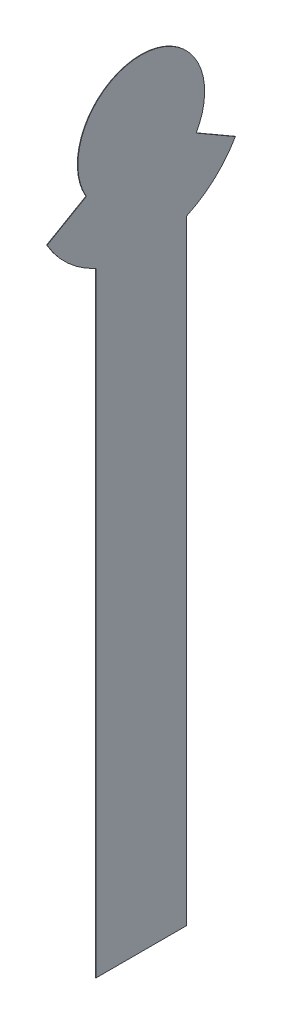
SolidWorks part; units mm, degrees
ref_plane "Front Plane" through (0, 0, 0) normal (0, 0, 1) x (1, 0, 0)
ref_plane "Top Plane" through (0, 0, 0) normal (0, 1, 0) x (1, 0, 0)
ref_plane "Right Plane" through (0, 0, 0) normal (1, 0, 0) x (0, 0, -1)
sketch "Sketch1" plane through (0, 0, 0) normal (1, 0, 0) x (0, 0, -1)
  line L0 (0, -35) -> (0, -393.6) construction
  line L1 (-25, -393.6) -> (25, -393.6) construction
  line L2 (-25, -393.6) -> (-25, -54.5436)
  line L3 (25, -393.6) -> (25, -54.5436)
  line L4 (-30.3109, -17.5) -> (-51.9615, -30)
  line L5 (30.3109, -17.5) -> (51.9615, -30)
  line L6 (-14.9027, 0) -> (13.6443, 0) construction
  line L7 (-25, -393.6) -> (25, -393.6)
  arc A0 (-51.9615, -30) -> (51.9615, -30) centre (0, 0) ccw
  circle A1 centre (0, 0) radius 35
  point P8 (0, -393.6)
  dimension "D1" = 120
  dimension "D2" = 70
  dimension "D3" = 393.6
  dimension "D4" = 50
  dimension "D5" = 30
  dimension "D6" = 30
extrude "Boss-Extrude1" add sketch "Sketch1" against normal blind 0.25 contours A0 L2 L7 L3 | A1 L4 A0 L5 | A1 region at (0, -225.9039, 0) region at (0, -40.189, 0) region at (0, 0, 0)
